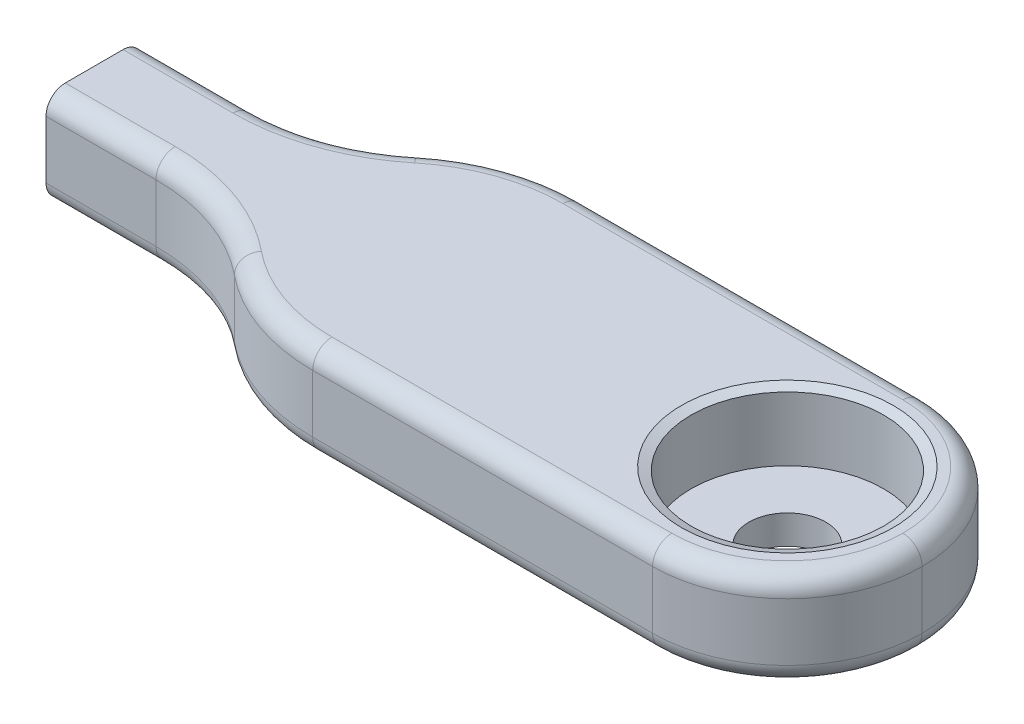
SolidWorks part; units mm, degrees
ref_plane "Спереди" through (0, 0, 0) normal (0, 0, 1) x (1, 0, 0)
ref_plane "Сверху" through (0, 0, 0) normal (0, 1, 0) x (1, 0, 0)
ref_plane "Справа" through (0, 0, 0) normal (1, 0, 0) x (0, 0, -1)
sketch "Эскиз2" plane through (0, 0, 0) normal (0, 1, 0) x (1, 0, 0)
  line L1 (-21.5, -7) -> (21.5, -7)
  line L2 (-21.5, -7) -> (-21.5, 7)
  line L3 (-21.5, 7) -> (21.5, 7)
  line L4 (21.5, -7) -> (21.5, 7)
  line L5 (-21.5, -7) -> (21.5, 7) construction
  line L6 (-21.5, 7) -> (21.5, -7) construction
  point P0 (0, 0)
  dimension "D1" = 43
  dimension "D2" = 14
extrude "Бобышка-Вытянуть1" add sketch "Эскиз2" along normal blind 5
sketch "Эскиз6" plane through (0, 5, 0) normal (0, 1, 0) x (1, 0, 0)
  line L0 (21.5, -7) -> (21.5, 7) construction
  circle A0 centre (14.5, 0) radius 5
  dimension "D1" = 10
  dimension "D2" = 7
extrude "Вырез-Вытянуть4" cut sketch "Эскиз6" against normal blind 3.5
sketch "Эскиз7" plane through (0, 5, 0) normal (0, 1, 0) x (1, 0, 0)
  line L0 (-29.7674, 0) -> (0, 0) construction
  line L1 (-21.5, -2.5) -> (-11.5, -2.5)
  line L2 (-21.5, 7) -> (-11.5, 7)
  line L3 (-21.5, 7) -> (-21.5, 2.5)
  line L4 (-21.5, 2.5) -> (-11.5, 2.5)
  line L5 (-11.5, 7) -> (-11.5, 2.5)
  line L6 (-11.5, -7) -> (-11.5, -2.5)
  line L7 (-21.5, -7) -> (-11.5, -7)
  line L8 (-21.5, -7) -> (-21.5, -2.5)
  dimension "D1" = 10
  dimension "D2" = 4.5
extrude "Вырез-Вытянуть5" cut sketch "Эскиз7" against normal blind 10
fillet "Скругление1" radius 10 2 edges at (-11.5, 2.5, 7) (-11.5, 2.5, -7)
fillet "Скругление2" radius 10 2 edges at (-11.5, 2.5, -2.5) (-11.5, 2.5, 2.5)
fillet "Скругление4" radius 7 2 edges at (21.5, 2.5, -7) (21.5, 2.5, 7)
chamfer "Фаска1" distance 0.5 angle 20 1 edges at (14.5, 5, 5) first distance on face at (14.5, 5, 5)
fillet "Скругление3" radius 1 20 edges at (5.6758, 0, -7) (-6.5025, 0, -6.4207) (-12.4335, 0, -3.0793) (5.6758, 5, -7) (-6.5025, 5, -6.4207) (-12.4335, 5, -3.0793) (5.6758, 0, 7) (-6.5025, 0, 6.4207) (-12.4335, 0, 3.0793) (5.6758, 5, 7) (-6.5025, 5, 6.4207) (-12.4335, 5, 3.0793) (-18.6438, 0, -2.5) (-18.6438, 5, -2.5) (-18.6438, 0, 2.5) (-18.6438, 5, 2.5) (19.4497, 0, -4.9497) (19.4497, 0, 4.9497) (19.4497, 5, -4.9497) (19.4497, 5, 4.9497)
sketch "Эскиз8" plane through (-21.5, 0, 0) normal (-1, 0, 0) x (0, 0, 1)
  circle A0 centre (0, 2.5) radius 2.2
  dimension "D1" = 4.4
extrude "Вырез-Вытянуть6" cut sketch "Эскиз8" against normal blind 3
fillet "Скругление5" radius 2 1 edges at (-18.5, 2.5, 2.2)
sketch "Эскиз9" plane through (0, 1.5, 0) normal (0, 1, 0) x (1, 0, 0)
  circle A0 centre (14.5, 0) radius 2
extrude "Вырез-Вытянуть7" cut sketch "Эскиз9" against normal blind 4
